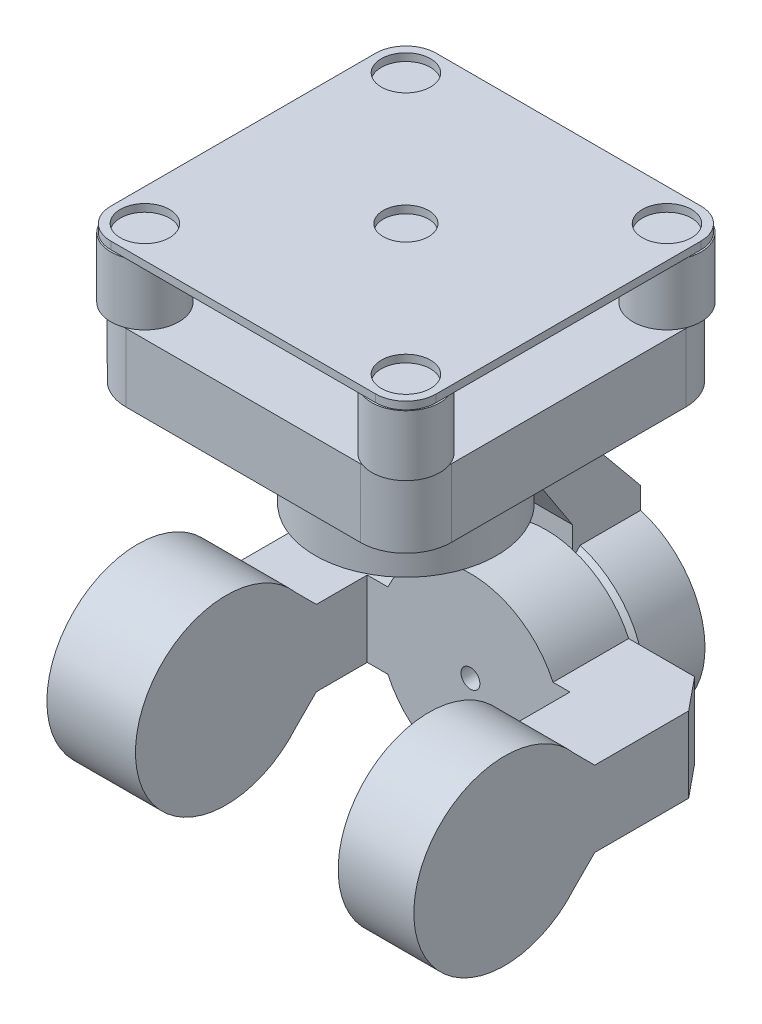
SolidWorks part; units mm, degrees
ref_plane "Front Plane" through (0, 0, 0) normal (0, 0, 1) x (1, 0, 0)
ref_plane "Top Plane" through (0, 0, 0) normal (0, 1, 0) x (1, 0, 0)
ref_plane "Right Plane" through (0, 0, 0) normal (1, 0, 0) x (0, 0, -1)
sketch "Sketch1" plane through (0, 0, 0) normal (0, 1, 0) x (1, 0, 0)
  line L1 (-17.5, -21.5) -> (17.5, -21.5)
  line L2 (-21.5, -17.5) -> (-21.5, 17.5)
  line L3 (-17.5, 21.5) -> (17.5, 21.5)
  line L4 (21.5, -17.5) -> (21.5, 17.5)
  line L5 (-21.5, -21.5) -> (21.5, 21.5) construction
  line L6 (-21.5, 21.5) -> (21.5, -21.5) construction
  line L7 (17.25, -17.25) -> (-17.25, -17.25) construction
  line L8 (17.25, -17.25) -> (17.25, 17.25) construction
  line L9 (17.25, 17.25) -> (-17.25, 17.25) construction
  line L10 (-17.25, -17.25) -> (-17.25, 17.25) construction
  line L11 (17.25, -17.25) -> (-17.25, 17.25) construction
  line L12 (17.25, 17.25) -> (-17.25, -17.25) construction
  arc A0 (17.5, -21.5) -> (21.5, -17.5) centre (17.5, -17.5) ccw
  arc A1 (-17.5, -21.5) -> (-21.5, -17.5) centre (-17.5, -17.5) cw
  arc A2 (-21.5, 17.5) -> (-17.5, 21.5) centre (-17.5, 17.5) cw
  arc A3 (17.5, 21.5) -> (21.5, 17.5) centre (17.5, 17.5) cw
  circle A4 centre (-17.25, 17.25) radius 3.25
  circle A5 centre (17.25, 17.25) radius 3.25
  circle A6 centre (17.25, -17.25) radius 3.25
  circle A7 centre (-17.25, -17.25) radius 3.25
  point P0 (0, 0)
  point P18 (0, 0)
  dimension "D2" = 4
  dimension "D4" = 6.5
  dimension "D1" = 43
  dimension "D3" = 34.5
extrude "Boss-Extrude1" add sketch "Sketch1" along normal blind 1
sketch "Sketch3" plane through (0, 0, 0) normal (0, -1, 0) x (1, 0, 0)
  circle A0 centre (-17.25, 17.25) radius 4.5
  circle A1 centre (17.25, 17.25) radius 4.5
  circle A2 centre (17.25, -17.25) radius 4.5
  circle A3 centre (-17.25, -17.25) radius 4.5
  circle A4 centre (17.25, 17.25) radius 3.25 construction
  circle A5 centre (-17.25, -17.25) radius 3.25 construction
  dimension "D1" = 9
extrude "Boss-Extrude2" add sketch "Sketch3" along normal blind 8
sketch "Sketch4" plane through (0, -8, 0) normal (0, -1, 0) x (1, 0, 0)
  line L0 (-15.771, 21.5) -> (15.771, 21.5) construction
  line L1 (21.5, -21.5) -> (-21.5, -21.5)
  line L2 (21.5, -21.5) -> (21.5, 21.5)
  line L3 (21.5, 21.5) -> (-21.5, 21.5)
  line L4 (-21.5, -21.5) -> (-21.5, 21.5)
  line L5 (21.5, -21.5) -> (-21.5, 21.5) construction
  line L6 (21.5, 21.5) -> (-21.5, -21.5) construction
  line L7 (-21.5, -15.771) -> (-21.5, 15.771) construction
  point P0 (0, 0)
extrude "Boss-Extrude3" add sketch "Sketch4" along normal blind 9
fillet "Fillet1" radius 6 4 edges at (21.5, -12.5, 21.5) (21.5, -12.5, -21.5) (-21.5, -12.5, -21.5) (-21.5, -12.5, 21.5)
sketch "Sketch5" plane through (0, -17, 0) normal (0, -1, 0) x (1, 0, 0)
  circle A0 centre (0, 0) radius 12
  dimension "D1" = 24
extrude "Boss-Extrude4" add sketch "Sketch5" along normal blind 14
sketch "Sketch6" plane through (0, -17, 0) normal (0, -1, 0) x (1, 0, 0)
  circle A0 centre (0, 0) radius 12 construction
  circle A1 centre (0, 0) radius 12
  circle A2 centre (0, 0) radius 11
  dimension "D1" = 1
extrude "Cut-Extrude1" cut sketch "Sketch6" against normal blind 1 from offset 8
sketch "Sketch7" plane through (0, 0, 0) normal (1, 0, 0) x (0, 0, -1)
  line L0 (0, -25) -> (14.3688, -25)
  line L1 (12, -25) -> (-12, -25) construction
  line L2 (14.3688, -25) -> (27.5275, -41)
  line L3 (27.5275, -41) -> (27.5275, -66.7886)
  line L4 (27.5275, -66.7886) -> (18.5275, -66.7886)
  line L5 (18.5275, -66.7886) -> (18.5275, -41)
  line L6 (18.5275, -41) -> (12, -31)
  line L7 (12, -31) -> (12, -25) construction
  line L8 (-12, -31) -> (12, -31) construction
  line L9 (12, -31) -> (0, -31)
  line L10 (0, -31) -> (0, -25)
  dimension "D1" = 9
  dimension "D2" = 10
extrude "Boss-Extrude5" add sketch "Sketch7" along normal mid plane 7
fillet "Fillet2" radius 4 1 edges at (0, -31, -12)
sketch "Sketch8" plane through (0, 0, -18.5275) normal (0, 0, 1) x (1, 0, 0)
  circle A0 centre (0, -55.3104) radius 12
  dimension "D1" = 24
extrude "Boss-Extrude6" add sketch "Sketch8" against normal up to surface (9 mm away) up to face at (0, -53.8943, -27.5275)
chamfer "Chamfer1" distance 1 angle 45 1 edges at (0, -67.3104, -18.5275)
sketch "Sketch10" plane through (0, 0, -18.5275) normal (0, 0, 1) x (1, 0, 0)
  circle A0 centre (0, -55.3104) radius 12
  arc A1 (-3.5, -43.8321) -> (3.5, -43.8321) centre (0, -55.3104) ccw construction
extrude "Boss-Extrude7" add sketch "Sketch10" along normal blind 10
ref_axis "Axis1" through (0, -55.3104, -8.5275) along (0, 0, -1)
ref_plane "Plane2" through (0, -55.3104, 0) normal (0, 1, 0) x (1, 0, 0)
sketch "Sketch11" plane through (0, -55.3104, 0) normal (0, 1, 0) x (1, 0, 0)
  line L0 (-13.6386, -5.3522) -> (-13.6386, 8.5275)
  line L1 (-13.6386, 8.5275) -> (13.1505, 8.5275)
  line L2 (13.1505, 8.5275) -> (13.1505, -5.3522)
  line L3 (13.1505, -5.3522) -> (23.154, -5.3522)
  line L4 (23.154, -5.3522) -> (23.154, 14.2125)
  line L5 (23.154, 14.2125) -> (19.621, 18.5275)
  line L6 (19.621, 18.5275) -> (-23.6421, 18.5275)
  line L7 (-23.6421, 18.5275) -> (-23.6421, -5.3522)
  line L8 (-23.6421, -5.3522) -> (-13.6386, -5.3522)
  line L9 (11, 18.5275) -> (-11, 18.5275) construction
  line L10 (-12, 8.5275) -> (12, 8.5275) construction
extrude "Boss-Extrude8" add sketch "Sketch11" along normal mid plane 10
sketch "Sketch12" plane through (23.154, 0, 0) normal (1, 0, 0) x (0, 0, -1)
  line L0 (-5.3522, -50.3104) -> (-5.3522, -60.3104) construction
  circle A0 centre (-10.1052, -55.3104) radius 12
  point P4 (-5.3522, -55.3104)
  dimension "D1" = 24
extrude "Boss-Extrude9" add sketch "Sketch12" against normal blind 48.5
sketch "Sketch13" plane through (0, -60.3104, 0) normal (0, -1, 0) x (1, 0, 0)
  line L0 (13.1505, -8.5275) -> (13.1505, -0.8035) construction
  line L1 (-13.6386, -8.5275) -> (13.1505, -8.5275)
  line L2 (-13.6386, -8.5275) -> (-13.6386, 39.8305)
  line L3 (-13.6386, 39.8305) -> (13.1505, 39.8305)
  line L4 (13.1505, -8.5275) -> (13.1505, 39.8305)
extrude "Cut-Extrude2" cut sketch "Sketch13" against normal blind 20 and the other way through all
ref_plane "Plane3" through (0, -66.5, 0) normal (0, 1, 0) x (1, 0, 0)
ref_plane "Plane4" through (0, 0, 21.4725) normal (0, 0, -1) x (-1, 0, 0)
sketch "Sketch14" plane through (0, 0, 0) normal (1, 0, 0) x (0, 0, -1)
  circle A0 centre (0, 0) radius 1.5
  dimension "D1" = 3
extrude "Boss-Extrude10" [suppressed] add sketch "Sketch14" along normal mid plane 60
chamfer "Chamfer2" distance 1 angle 45 2 edges at (-18.6404, -50.3104, -0.8035) (18.1522, -50.3104, -0.8035) first distance on face at (-16.0631, -50.3104, -9.2862) first distance on face at (16.2925, -50.3104, -9.9899)
chamfer "Chamfer4" distance 1 angle 45 1 edges at (18.1522, -60.3104, -0.8035) first distance on face at (16.2925, -60.3104, -9.9899)
chamfer "Chamfer5" distance 1 angle 45 1 edges at (-18.6404, -60.3104, -0.8035) first distance on face at (-16.0631, -60.3104, -9.2862)
ref_plane "Plane5" through (19.621, -60.3104, -18.5275) normal (0, -1, 0) x (-1, 0, 0)
sketch "Sketch17" plane through (0, 0, -27.5275) normal (0, 0, -1) x (-1, 0, 0)
  circle A0 centre (0, -55.3104) radius 1.25
  arc A1 (-3.5, -43.8321) -> (3.5, -43.8321) centre (0, -55.3104) ccw construction
  dimension "D1" = 2.5
extrude "Cut-Extrude4" cut sketch "Sketch17" against normal through all
sketch "Sketch16" plane through (0, 0, 0) normal (1, 0, 0) x (0, 0, -1)
  line L0 (18.5275, -41.5648) -> (18.5275, -67.3952)
  line L1 (18.5275, -67.3952) -> (42.5612, -67.3952)
  line L2 (42.5612, -67.3952) -> (41.4337, 8.6048)
  line L3 (41.4337, 8.6048) -> (-25.3031, 8.6048)
  line L4 (-25.3031, 8.6048) -> (-25.3031, -33.7242)
  line L5 (-25.3031, -33.7242) -> (18.5275, -41.5648)
  line L6 (18.5275, -67.3104) -> (18.5275, -60.3104) construction
extrude "Cut-Extrude3" [suppressed] cut sketch "Sketch16" against normal mid plane 72
chamfer "Chamfer6" [suppressed] distance 2 angle 45
sketch "Sketch18" plane through (0, 1, 0) normal (0, 1, 0) x (1, 0, 0)
  circle A0 centre (0, 0) radius 3
  dimension "D1" = 6
extrude "Cut-Extrude5" cut sketch "Sketch18" against normal up to next
sketch "Sketch19" plane through (0, -31, 0) normal (0, -1, 0) x (1, 0, 0)
  circle A0 centre (0, 0) radius 1.5
  dimension "D1" = 3
extrude "Cut-Extrude6" cut sketch "Sketch19" against normal through all
